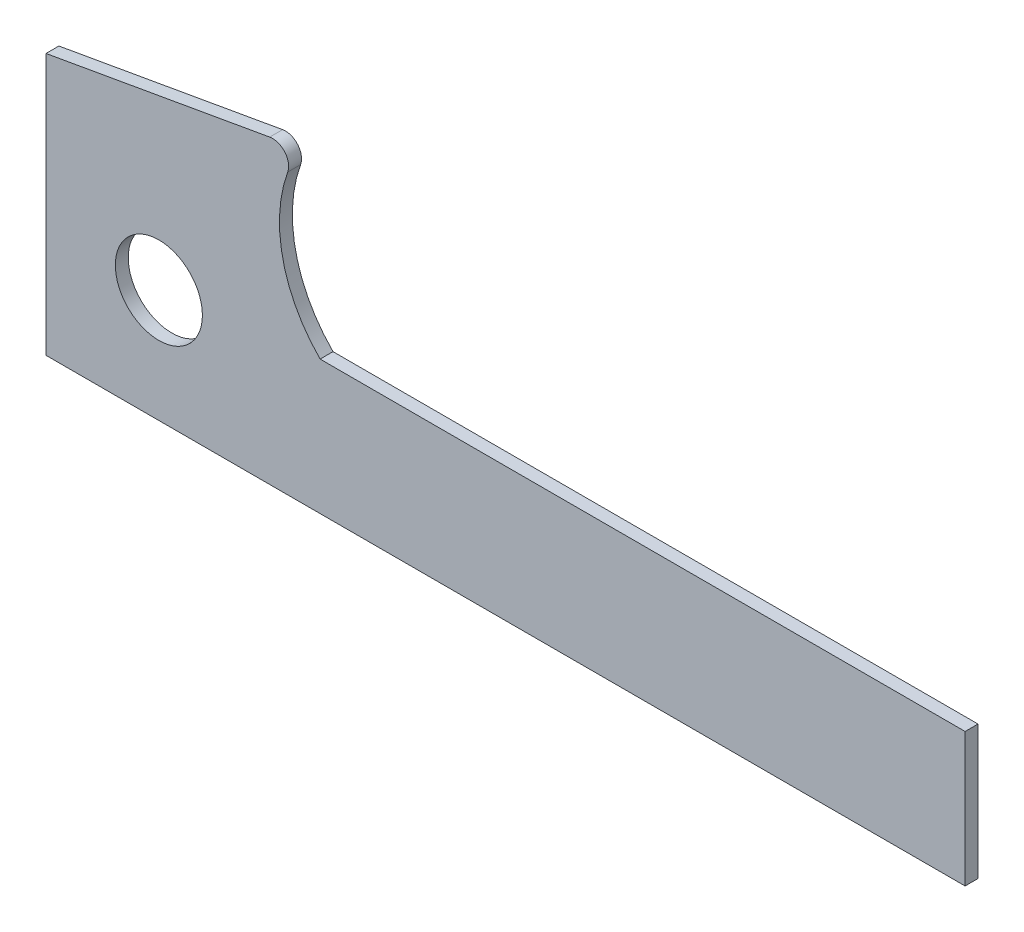
SolidWorks part; units mm, degrees
material "AISI 1020"
ref_plane "Спереди" through (0, 0, 0) normal (0, 0, 1) x (1, 0, 0)
ref_plane "Сверху" through (0, 0, 0) normal (0, 1, 0) x (1, 0, 0)
ref_plane "Справа" through (0, 0, 0) normal (1, 0, 0) x (0, 0, -1)
sketch "Эскиз1" plane through (0, 0, 0) normal (0, 0, 1) x (1, 0, 0)
  line L0 (0, -35) -> (0, 35) construction
  line L1 (0, -35) -> (250, -35)
  line L2 (-35, -35) -> (-35, 46.0724)
  line L4 (250, -35) -> (250, 6.5)
  line L5 (0, 0) -> (41.0255, 44.1517) construction
  line L6 (-17.2764, -30.4389) -> (17.2764, 30.4389) construction
  line L8 (-35, -35) -> (-35, -40) construction
  line L9 (-35, -40) -> (250, -40) construction
  line L10 (250, -40) -> (250, -35) construction
  line L12 (-35, -35) -> (0, -35)
  line L13 (200.1444, -153.8415) -> (-17.2764, -30.4389) construction
  line L14 (59.0098, 12.2599) -> (44.3327, 25) construction
  line L15 (44.3327, 25) -> (41.0255, 44.1517) construction
  line L16 (0, 0) -> (59.0098, 12.2599) construction
  line L17 (0, 0) -> (44.3327, 25) construction
  line L18 (0, 0) -> (44.3327, 25) construction
  line L19 (50, 6.5) -> (150, 6.5) construction
  line L20 (-35, 46.0724) -> (34.375, 58.305)
  line L21 (-1450, 65) -> (100, 65) construction
  line L22 (50, 6.5) -> (250, 6.5)
  circle A0 centre (41.0255, 44.1517) radius 3 construction
  circle A1 centre (44.3327, 25) radius 3 construction
  arc A2 (50, 6.5) -> (39.9479, 51.6881) centre (80.67, 37.0346) cw
  arc A3 (39.9479, 51.6881) -> (34.375, 58.305) centre (35.2433, 53.381) ccw
  circle A4 centre (0, 0) radius 13.5 construction
  circle A5 centre (0, 0) radius 13.5
  point P9 (0, 0)
  point P39 (43.9876, 60)
  dimension "D3" = 5
  dimension "D4" = 5
  dimension "D1" = 5
  dimension "D2" = 5
  dimension "100" = 100
base flange "Базовая кромка1" sketch "Эскиз1" thickness 4 reverse thickness direction no parameters "D1"=0.74
sketch "Сгиб-Линии1" [suppressed] plane through (0, 0, 0) normal (0, 1, 0) x (1, 0, 0)
sketch "Граничная рамка1" [suppressed] plane through (0, 0, 0) normal (0, 1, 0) x (1, 0, 0)
sheet metal parameters "Листовой металл3" thickness 4 parameters "D1"=0.74
flat pattern "Развертка3" [suppressed]
sketch "Сгиб-Линии2" plane through (0, 0, 0) normal (0, 1, 0) x (1, 0, 0)
sketch3d "Граничная рамка2" [suppressed]
  line L0 (-110.3946, 22.8207, 0) -> (174.6054, 22.8207, 0) construction
  line L1 (-110.3946, -70.3104, 0) -> (174.6054, -70.3104, 0) construction
  line L2 (-110.3946, 22.8207, 0) -> (-110.3946, -70.3104, 0) construction
  line L3 (174.6054, 22.8207, 0) -> (174.6054, -70.3104, 0) construction
